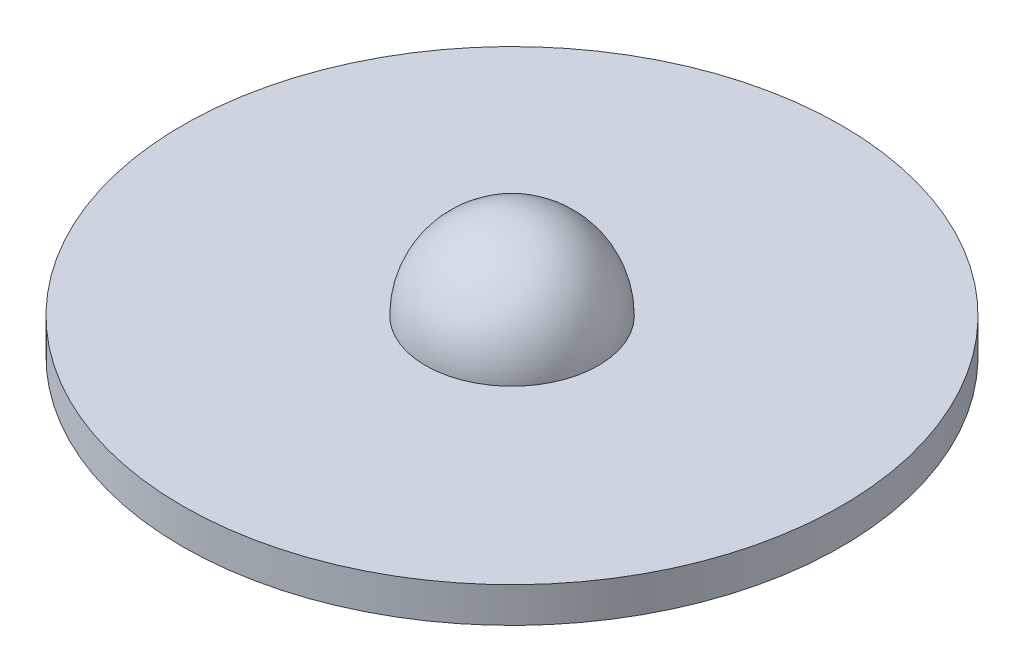
SolidWorks part; units mm, degrees
ref_plane "前视基准面" through (0, 0, 0) normal (0, 0, 1) x (1, 0, 0)
ref_plane "上视基准面" through (0, 0, 0) normal (0, 1, 0) x (1, 0, 0)
ref_plane "右视基准面" through (0, 0, 0) normal (1, 0, 0) x (0, 0, -1)
other "Configuration Table"
sketch "草图1" plane through (0, 0, 0) normal (0, 1, 0) x (1, 0, 0)
  line L0 (0, 2.1) -> (0, -2.1)
  arc A0 (0, -2.1) -> (0, 2.1) centre (0, 0) ccw
  dimension "D1" = 4.2
revolve "旋转1" add sketch "草图1" angle 180 about L0
sketch "草图6" plane through (0, 0, 0) normal (1, 0, 0) x (0, 0, -1)
  line L1 (0, 0) -> (8, 0)
  line L2 (0, 0) -> (0, -0.8562)
  line L3 (0, -0.8562) -> (8, -0.8562)
  line L4 (8, 0) -> (8, -0.8562)
  dimension "D1" = 8
revolve "旋转2" add sketch "草图6" angle 360 about L2
sketch "草图7" plane through (0, 0, 0) normal (1, 0, 0) x (0, 0, -1)
  line L0 (-8, -0.8562) -> (8, -0.8562) construction
  line L1 (0, -0.1037) -> (7.9, -0.1037)
  line L2 (0, -0.1037) -> (0, -0.8562)
  line L3 (0, -0.8562) -> (7.9, -0.8562)
  line L4 (7.9, -0.1037) -> (7.9, -0.8562)
  dimension "D1" = 7.9
revolve "切除-旋转2" cut sketch "草图7" angle 360 about L2
